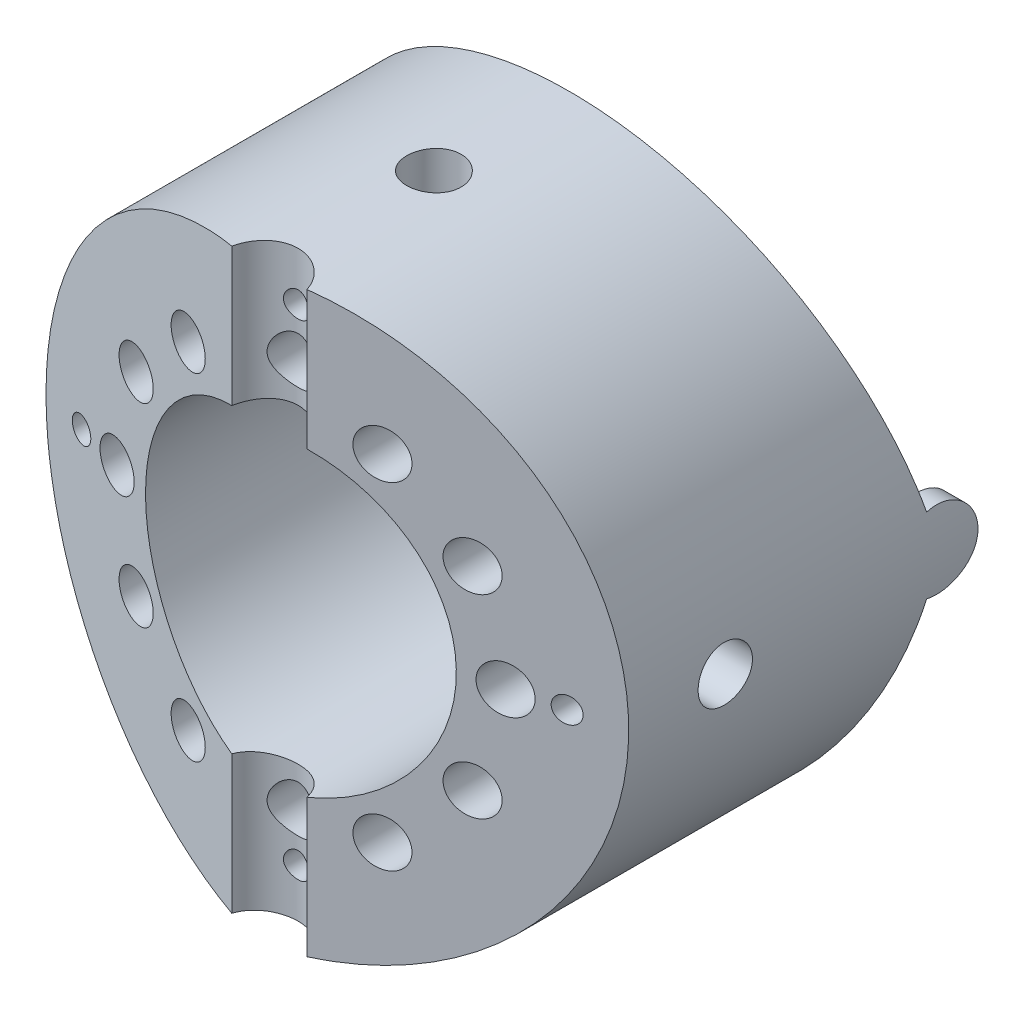
SolidWorks part; units mm, degrees
ref_plane "前视基准面" through (0, 0, 0) normal (0, 0, 1) x (1, 0, 0)
ref_plane "上视基准面" through (0, 0, 0) normal (0, 1, 0) x (1, 0, 0)
ref_plane "右视基准面" through (0, 0, 0) normal (1, 0, 0) x (0, 0, -1)
sketch "草图1" plane through (0, 0, 0) normal (0, 0, 1) x (1, 0, 0)
  circle A0 centre (0, 0) radius 7.5
  dimension "D1" = 15
extrude "凸台-拉伸1" add sketch "草图1" along normal blind 10
sketch "草图2" plane through (0, 0, 0) normal (1, 0, 0) x (0, 0, -1)
  line L0 (0, 0) -> (-2.0096, 7.5)
  line L1 (0, 7.5) -> (-10, 7.5) construction
  line L2 (-2.0096, 7.5) -> (0, 7.5)
  line L3 (0, 7.5) -> (0, 0)
  line L4 (0, 0) -> (-2.0096, -7.5)
  line L5 (-10, -7.5) -> (0, -7.5) construction
  line L6 (-2.0096, -7.5) -> (0, -7.5)
  line L7 (0, -7.5) -> (0, 0)
  dimension "D1" = 15
  dimension "D2" = 15
extrude "切除-拉伸1" cut sketch "草图2" against normal through all and the other way through all contours L3 L2 L0 | L6 L7 L4 region at (0, 5, 0.6699) region at (0, -5, 0.6699)
sketch "草图3" plane through (0, 0, 0) normal (0, 1, 0) x (1, 0, 0)
  line L0 (0, 0) -> (0, -10) construction
  line L1 (-7.5, -10) -> (7.5, -10) construction
  line L2 (0, -10) -> (7.5, -10)
  line L3 (7.5, -10) -> (7.5, -7.9904)
  line L4 (7.5, -7.9904) -> (0, -10)
  line L5 (0, -10) -> (-7.5, -7.9904)
  line L6 (-7.5, 0) -> (-7.5, -10) construction
  line L7 (-7.5, -7.9904) -> (-7.5, -10)
  line L8 (-7.5, -10) -> (0, -10)
  dimension "D1" = 15
  dimension "D2" = 15
extrude "切除-拉伸2" cut sketch "草图3" against normal through all and the other way through all contours L3 L4 L2 | L7 L8 L5 region at (5, 0, 9.3301) region at (-5, 0, 9.3301)
sketch "草图6" plane through (0, 0, 0) normal (1, 0, 0) x (0, 0, -1)
  circle A0 centre (0, 0) radius 1
  dimension "D1" = 2
extrude "凸台-拉伸2" add sketch "草图6" against normal up to surface and the other way up to surface up to face at (0, 0, 7.9904) other way up to face at (0, 0, 7.9904)
sketch "草图7" plane through (0, 0, 0) normal (0, 1, 0) x (1, 0, 0)
  circle A0 centre (0, -10) radius 1
  dimension "D1" = 2
extrude "切除-拉伸7" cut sketch "草图7" against normal through all and the other way through all
sketch "草图8" plane through (0, 0, 0) normal (0, 0, 1) x (1, 0, 0)
  circle A0 centre (0, 0) radius 4
  dimension "D1" = 8
extrude "切除-拉伸9" cut sketch "草图8" against normal through all and the other way through all
sketch "草图9" plane through (0, 0, 0) normal (0, 0, 1) x (1, 0, 0)
  line L0 (0, 0) -> (-5, 0) construction
  circle A0 centre (0, 0) radius 5 construction
  circle A1 centre (-5, 0) radius 0.6
  circle A2 centre (-4.3301, 2.5) radius 0.6
  circle A3 centre (-2.5, 4.3301) radius 0.6
  circle A4 centre (0, 5) radius 0.6
  circle A5 centre (2.5, 4.3301) radius 0.6
  circle A6 centre (4.3301, 2.5) radius 0.6
  circle A7 centre (5, 0) radius 0.6
  circle A8 centre (4.3301, -2.5) radius 0.6
  circle A9 centre (2.5, -4.3301) radius 0.6
  circle A10 centre (0, -5) radius 0.6
  circle A11 centre (-2.5, -4.3301) radius 0.6
  circle A12 centre (-4.3301, -2.5) radius 0.6
  point P29 (0, 0)
  dimension "D1" = 10
  dimension "D2" = 1.2
  dimension "D3" = 12
extrude "切除-拉伸10" cut sketch "草图9" against normal through all and the other way through all
sketch "草图10" plane through (0, 0, 0) normal (0, 0, 1) x (1, 0, 0)
  line L0 (0, 0) -> (-6.25, 0) construction
  circle A0 centre (0, 0) radius 6.25 construction
  circle A1 centre (-6.25, 0) radius 0.325
  circle A2 centre (0, 6.25) radius 0.325
  circle A3 centre (6.25, 0) radius 0.325
  circle A4 centre (0, -6.25) radius 0.325
  point P14 (0, 0)
  dimension "D1" = 12.5
  dimension "D2" = 0.65
  dimension "D3" = 4
extrude "切除-拉伸11" cut sketch "草图10" against normal through all and the other way through all
ref_plane "基准面1" through (0, 0, -1) normal (0, 0, -1) x (-1, 0, 0)
sketch "草图11" plane through (0, 0, -1) normal (0, 0, -1) x (-1, 0, 0)
  line L0 (-5.6596, -0.9659) -> (-5.6596, 0.9659) construction
  line L1 (-3.8816, -0.9659) -> (-7.4375, -0.9659) construction
  line L2 (-7.433, -1) -> (-3.873, -1) construction
  line L3 (-4.4096, -1) -> (-6.9096, -1)
  line L4 (-4.4096, -1) -> (-4.4096, 1)
  line L5 (-4.4096, 1) -> (-6.9096, 1)
  line L6 (-6.9096, -1) -> (-6.9096, 1)
  line L7 (-4.4096, -1) -> (-6.9096, 1) construction
  line L8 (-4.4096, 1) -> (-6.9096, -1) construction
  line L9 (-3.873, 1) -> (-7.433, 1) construction
  line L10 (0, 0) -> (0, 7.5) construction
  line L11 (4.4096, -1) -> (6.9096, -1)
  line L12 (6.9096, -1) -> (6.9096, 1)
  line L13 (4.4096, 1) -> (6.9096, 1)
  line L14 (4.4096, -1) -> (4.4096, 1)
  arc A0 (7.4375, 0.9659) -> (-7.4375, 0.9659) centre (0, 0) ccw construction
  point P4 (-5.6596, 0)
  dimension "D1" = 2.5
extrude "切除-拉伸12" cut sketch "草图11" against normal blind 1
ref_plane "基准面2" through (0, -7.5, 0) normal (0, -1, 0) x (-1, 0, 0)
sketch "草图12" plane through (0, -7.5, 0) normal (0, -1, 0) x (-1, 0, 0)
  line L0 (0, -9) -> (0, -2.0096) construction
  arc A0 (0.9659, -9.7412) -> (-0.9659, -9.7412) centre (0, -10) ccw construction
  circle A1 centre (0, -5.5048) radius 0.7
  ellipse E0 centre (0, 0) end of major axis (-7.5, 0) minor radius 2.0096 (-7.4375, -0.2588) -> (7.4375, -0.2588) ccw construction
  dimension "D1" = 1.4
extrude "切除-拉伸13" cut sketch "草图12" against normal blind 1.25
pattern_circular "阵列(圆周)1" count 4 over 360 about axis through (0, 0, 10) along (0, 0, -1) of "切除-拉伸13"
